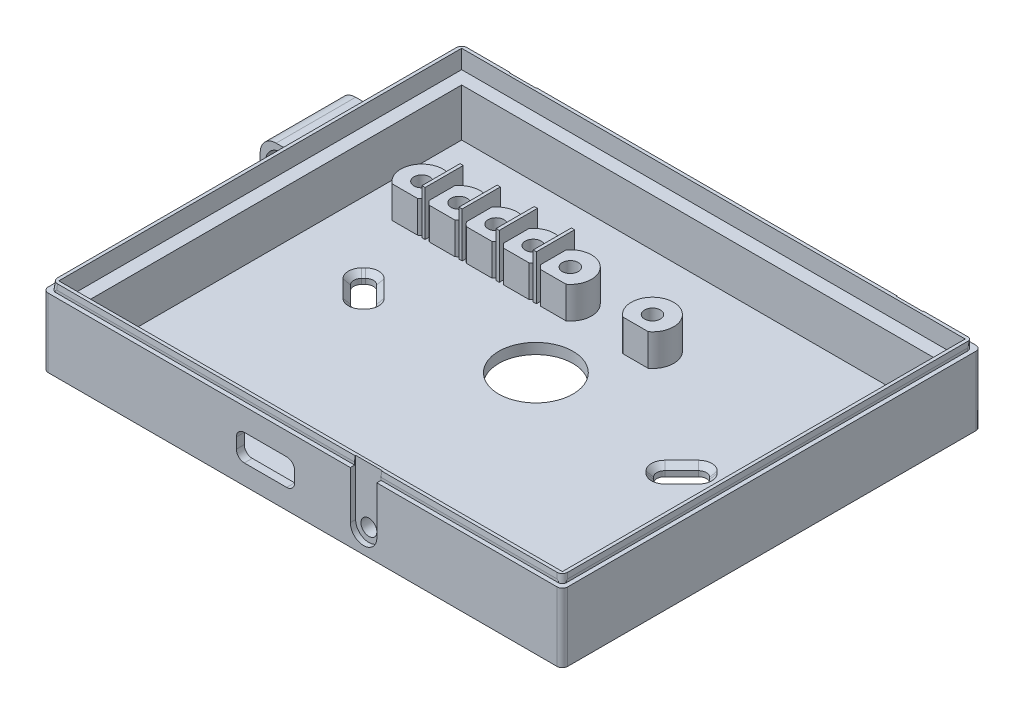
SolidWorks part; units mm, degrees
ref_plane "Alzado" through (0, 0, 0) normal (0, 0, 1) x (1, 0, 0)
ref_plane "Planta" through (0, 0, 0) normal (0, 1, 0) x (1, 0, 0)
ref_plane "Vista lateral" through (0, 0, 0) normal (1, 0, 0) x (0, 0, -1)
sketch "Croquis1" plane through (0, 0, 0) normal (0, 1, 0) x (1, 0, 0)
  line L1 (0, 0) -> (98, 0)
  line L2 (0, 0) -> (0, 79)
  line L3 (0, 79) -> (98, 79)
  line L4 (98, 0) -> (98, 79)
  line L5 (0, 0) -> (98, 79) construction
  line L6 (0, 79) -> (98, 0) construction
  point P4 (49, 39.5)
  dimension "D1" = 98
  dimension "D2" = 79
extrude "Saliente-Extruir1" add sketch "Croquis1" along normal blind 13
sketch "Croquis2" plane through (0, 13, 0) normal (0, 1, 0) x (1, 0, 0)
  line L0 (98, 0) -> (98, 79) construction
  line L1 (1.5, 77.5) -> (96.5, 77.5)
  line L2 (1.5, 77.5) -> (1.5, 1.5)
  line L3 (1.5, 1.5) -> (96.5, 1.5)
  line L4 (96.5, 77.5) -> (96.5, 1.5)
  line L5 (1.5, 77.5) -> (96.5, 1.5) construction
  line L6 (1.5, 1.5) -> (96.5, 77.5) construction
  line L7 (98, 79) -> (0, 79) construction
  point P4 (49, 39.5)
  dimension "D1" = 95
  dimension "D2" = 76
  dimension "D3" = 1.5
  dimension "D4" = 1.5
extrude "Cortar-Extruir1" cut sketch "Croquis2" against normal blind 11
sketch "Croquis3" plane through (0, 2, 0) normal (0, 1, 0) x (1, 0, 0)
  line L0 (24.5, 4) -> (24.5, 1.5)
  line L1 (1.5, 77.5) -> (96.5, 77.5)
  line L2 (1.5, 77.5) -> (1.5, 1.5)
  line L3 (1.5, 1.5) -> (24.5, 1.5)
  line L4 (96.5, 77.5) -> (96.5, 1.5)
  line L5 (1.5, 77.5) -> (96.5, 1.5) construction
  line L6 (1.5, 1.5) -> (96.5, 77.5) construction
  line L7 (4, 75) -> (94, 75)
  line L8 (4, 75) -> (4, 4)
  line L9 (4, 4) -> (24.5, 4)
  line L10 (94, 75) -> (94, 4)
  line L11 (4, 75) -> (94, 4) construction
  line L12 (4, 4) -> (94, 75) construction
  line L13 (58.5, 4) -> (58.5, 1.5)
  line L14 (58.5, 4) -> (94, 4)
  line L15 (58.5, 1.5) -> (96.5, 1.5)
  point P4 (49, 39.5)
  point P11 (49, 39.5)
  dimension "D1" = 2.5
  dimension "D2" = 2.5
  dimension "D3" = 2.5
  dimension "D4" = 2.5
  dimension "D5" = 38
  dimension "D6" = 23
extrude "Saliente-Extruir2" add sketch "Croquis3" along normal blind 9
sketch "Croquis4" plane through (0, 2, 0) normal (0, 1, 0) x (1, 0, 0)
  line L0 (13, 58.5) -> (56.5, 58.5) construction
  line L1 (96.5, 77.5) -> (1.5, 77.5) construction
  line L2 (1.5, 77.5) -> (1.5, 1.5) construction
  line L3 (10.6, 55.3) -> (15.4, 55.3)
  line L8 (54.1, 55.3) -> (58.9, 55.3)
  line L9 (17.6, 55.3) -> (22.4, 55.3)
  line L10 (24.6, 55.3) -> (29.4, 55.3)
  line L11 (31.6, 55.3) -> (36.4, 55.3)
  line L12 (38.6, 55.3) -> (43.4, 55.3)
  arc A0 (16.5, 60.4365) -> (10.6, 55.3) centre (13, 58.5) ccw
  arc A1 (16.5, 56.5635) -> (17.6, 55.3) centre (20, 58.5) ccw
  arc A2 (23.5, 56.5635) -> (24.6, 55.3) centre (27, 58.5) ccw
  arc A3 (30.5, 56.5635) -> (31.6, 55.3) centre (34, 58.5) ccw
  arc A4 (37.5, 56.5635) -> (38.6, 55.3) centre (41, 58.5) ccw
  arc A5 (58.9, 55.3) -> (54.1, 55.3) centre (56.5, 58.5) ccw
  arc A6 (23.5, 60.4365) -> (16.5, 60.4365) centre (20, 58.5) ccw
  arc A7 (30.5, 60.4365) -> (23.5, 60.4365) centre (27, 58.5) ccw
  arc A8 (37.5, 60.4365) -> (30.5, 60.4365) centre (34, 58.5) ccw
  circle A9 centre (13, 58.5) radius 1.5
  circle A10 centre (20, 58.5) radius 1.5
  circle A11 centre (27, 58.5) radius 1.5
  circle A12 centre (34, 58.5) radius 1.5
  circle A13 centre (41, 58.5) radius 1.5
  circle A14 centre (56.5, 58.5) radius 1.5
  arc A15 (15.4, 55.3) -> (16.5, 56.5635) centre (13, 58.5) ccw
  arc A16 (22.4, 55.3) -> (23.5, 56.5635) centre (20, 58.5) ccw
  arc A17 (29.4, 55.3) -> (30.5, 56.5635) centre (27, 58.5) ccw
  arc A18 (36.4, 55.3) -> (37.5, 56.5635) centre (34, 58.5) ccw
  arc A19 (43.4, 55.3) -> (37.5, 60.4365) centre (41, 58.5) ccw
  point P29 (27, 59.0244)
  dimension "D3" = 8
  dimension "D9" = 3
  dimension "D10" = 4
  dimension "D12" = 4
  dimension "D13" = 4
  dimension "D14" = 4
  dimension "D15" = 4
  dimension "D1" = 19
  dimension "D2" = 11.5
  dimension "D4" = 7
  dimension "D5" = 7
  dimension "D6" = 7
  dimension "D7" = 7
  dimension "D8" = 15.5
  dimension "D11" = 3.2
extrude "Saliente-Extruir3" add sketch "Croquis4" along normal blind 6
sketch "Croquis6" plane through (0, 2, 0) normal (0, 1, 0) x (1, 0, 0)
  line L0 (23.2, 62.5) -> (23.2, 55.3)
  line L1 (16.2, 62.5) -> (16.8, 62.5)
  line L2 (16.2, 62.5) -> (16.2, 55.3)
  line L3 (16.2, 55.3) -> (16.8, 55.3)
  line L4 (16.8, 62.5) -> (16.8, 55.3)
  line L5 (16.2, 62.5) -> (16.8, 55.3) construction
  line L6 (16.2, 55.3) -> (16.8, 62.5) construction
  line L7 (23.2, 62.5) -> (23.8, 62.5)
  line L8 (23.8, 62.5) -> (23.8, 55.3)
  line L9 (23.2, 55.3) -> (23.8, 55.3)
  line L10 (30.2, 62.5) -> (30.2, 55.3)
  line L11 (30.2, 62.5) -> (30.8, 62.5)
  line L12 (30.8, 62.5) -> (30.8, 55.3)
  line L13 (30.2, 55.3) -> (30.8, 55.3)
  line L14 (37.2, 62.5) -> (37.2, 55.3)
  line L15 (37.2, 62.5) -> (37.8, 62.5)
  line L16 (37.8, 62.5) -> (37.8, 55.3)
  line L17 (37.2, 55.3) -> (37.8, 55.3)
  circle A0 centre (13, 58.5) radius 1.5 construction
  circle A2 centre (13, 58.5) radius 1.5 construction
  point P4 (16.5, 58.9)
  dimension "D4" = 4
  dimension "D1" = 0.6
  dimension "D3" = 3.5
  dimension "D6" = 3.2
  dimension "D5" = 4
extrude "Saliente-Extruir4" add sketch "Croquis6" along normal blind 8.5
sketch "Croquis7" plane through (0, 2, 0) normal (0, 1, 0) x (1, 0, 0)
  line L0 (98, 0) -> (98, 79) construction
  line L1 (98, 79) -> (0, 79) construction
  line L6 (15.1109, 42.9142) -> (20.4142, 37.6109)
  line L7 (15.1109, 42.9142) -> (17.5858, 45.3891)
  line L8 (20.4142, 37.6109) -> (22.8891, 40.0858)
  line L9 (17.5858, 45.3891) -> (22.8891, 40.0858)
  line L10 (15.1109, 42.9142) -> (22.8891, 40.0858) construction
  line L11 (20.4142, 37.6109) -> (17.5858, 45.3891) construction
  line L12 (1.5, 1.5) -> (24.5, 1.5) construction
  line L13 (4, 4) -> (24.5, 4) construction
  line L14 (75.1109, 40.0858) -> (80.4142, 45.3891)
  line L15 (75.1109, 40.0858) -> (77.5858, 37.6109)
  line L16 (80.4142, 45.3891) -> (82.8891, 42.9142)
  line L17 (77.5858, 37.6109) -> (82.8891, 42.9142)
  line L18 (75.1109, 40.0858) -> (82.8891, 42.9142) construction
  line L19 (80.4142, 45.3891) -> (77.5858, 37.6109) construction
  line L20 (1.5, 1.5) -> (96.5, 1.5) construction
  circle A0 centre (49, 44) radius 7
  point P9 (19, 41.5)
  point P12 (79, 41.5)
  dimension "D1" = 14
  dimension "D2" = 49
  dimension "D3" = 35
  dimension "D4" = 3.5
  dimension "D5" = 7.5
  dimension "D6" = 30
  dimension "D7" = 40
  dimension "D8" = 45
  dimension "D9" = 30
  dimension "D10" = 45
  dimension "D11" = 40
  dimension "D12" = 3.5
  dimension "D13" = 7.5
extrude "Cortar-Extruir2" cut sketch "Croquis7" against normal blind 7.5
fillet "Redondeo1" radius 1.5 8 edges at (15.1109, 1, -42.9142) (17.5858, 1, -45.3891) (22.8891, 1, -40.0858) (20.4142, 1, -37.6109) (80.4142, 1, -45.3891) (82.8891, 1, -42.9142) (75.1109, 1, -40.0858) (77.5858, 1, -37.6109)
chamfer "Chaflán1" distance 1 angle 45 16 edges at (80.2374, 2, -40.2626) (82.2678, 2, -42.9142) (77.5858, 2, -38.2322) (81.6517, 2, -44.1517) (76.3483, 2, -38.8483) (80.4142, 2, -44.7678) (75.7322, 2, -40.0858) (77.7626, 2, -42.7374) (17.7626, 2, -40.2626) (20.4142, 2, -38.2322) (15.7322, 2, -42.9142) (21.6517, 2, -38.8483) (16.3483, 2, -44.1517) (22.2678, 2, -40.0858) (17.5858, 2, -44.7678) (20.2374, 2, -42.7374)
sketch "Croquis8" plane through (0, 13, 0) normal (0, 1, 0) x (1, 0, 0)
  line L1 (1.5, 77.5) -> (96.5, 77.5)
  line L2 (1.5, 77.5) -> (1.5, 1.5)
  line L3 (1.5, 1.5) -> (96.5, 1.5)
  line L4 (96.5, 77.5) -> (96.5, 1.5)
  line L5 (1.5, 77.5) -> (96.5, 1.5) construction
  line L6 (1.5, 1.5) -> (96.5, 77.5) construction
  line L7 (0.8, 78.2) -> (97.2, 78.2)
  line L8 (0.8, 78.2) -> (0.8, 0.8)
  line L9 (0.8, 0.8) -> (97.2, 0.8)
  line L10 (97.2, 78.2) -> (97.2, 0.8)
  line L11 (0.8, 78.2) -> (97.2, 0.8) construction
  line L12 (0.8, 0.8) -> (97.2, 78.2) construction
  point P4 (49, 39.5)
  point P11 (49, 39.5)
  dimension "D1" = 0.7
  dimension "D2" = 0.7
  dimension "D3" = 0.7
  dimension "D4" = 0.7
extrude "Saliente-Extruir6" add sketch "Croquis8" along normal blind 1.5
chamfer "Chaflán2" distance 1 angle 5 4 edges at (49, 14.5, -78.2) (0.8, 14.5, -39.5) (49, 14.5, -0.8) (97.2, 14.5, -39.5) first distance on face at (49, 13.75, -78.2) first distance on face at (0.8, 13.75, -39.5) first distance on face at (49, 13.75, -0.8) first distance on face at (97.2, 13.75, -39.5)
sketch "Croquis9" plane through (0, 0, 0) normal (0, 0, 1) x (1, 0, 0)
  line L1 (36.5, 8.75) -> (47.5, 8.75)
  line L2 (36.5, 8.75) -> (36.5, 3.75)
  line L3 (36.5, 3.75) -> (47.5, 3.75)
  line L4 (47.5, 8.75) -> (47.5, 3.75)
  line L5 (36.5, 8.75) -> (47.5, 3.75) construction
  line L6 (36.5, 3.75) -> (47.5, 8.75) construction
  line L7 (58.5, 11) -> (96.5, 11) construction
  line L8 (1.5, 11) -> (24.5, 11) construction
  line L9 (1.5, 11) -> (1.5, 14.5) construction
  line L10 (96.5, 11) -> (96.5, 14.5) construction
  line L11 (58.5, 11) -> (96.5, 11) construction
  line L12 (1.5, 11) -> (24.5, 11) construction
  line L13 (1.5, 11) -> (1.5, 14.5) construction
  line L14 (96.5, 11) -> (96.5, 14.5) construction
  point P4 (42, 6.25)
  dimension "D1" = 49
  dimension "D2" = 35
  dimension "D3" = 5
  dimension "D4" = 4.5
extrude "Cortar-Extruir3" cut sketch "Croquis9" against normal blind 10
fillet "Redondeo2" radius 1 8 edges at (0.8437, 14, -78.1563) (0.8437, 14, -0.8437) (97.1563, 14, -0.8437) (97.2, 13.25, -78.2) (98, 6.5, -79) (0, 6.5, -79) (0, 6.5, 0) (98, 6.5, 0)
fillet "Redondeo3" radius 1.5 4 edges at (36.5, 8.75, -0.75) (36.5, 3.75, -0.75) (47.5, 3.75, -0.75) (47.5, 8.75, -0.75)
ref_plane "Plano1" through (0, 0, -64) normal (0, 0, -1) x (-1, 0, 0)
sketch "Croquis10" plane through (0, 0, -64) normal (0, 0, -1) x (-1, 0, 0)
  line L0 (0, 13) -> (0, 0) construction
  line L1 (0, 2) -> (8, 2)
  line L2 (0, 2) -> (0, 10)
  line L3 (0, 10) -> (8, 10)
  line L4 (8, 2) -> (8, 10)
  line L5 (0, 2) -> (8, 10) construction
  line L6 (0, 10) -> (8, 2) construction
  line L7 (-97, 0) -> (-1, 0) construction
  circle A0 centre (4, 6) radius 3
  point P4 (4, 6)
  dimension "D3" = 6
  dimension "D1" = 2
  dimension "D2" = 8
  dimension "D4" = 8
extrude "Saliente-Extruir7" add sketch "Croquis10" against normal blind 15
fillet "Redondeo4" radius 3 2 edges at (-8, 2, -56.5) (-8, 10, -56.5)
sketch "Croquis11" plane through (0, 0, -79) normal (0, 0, -1) x (-1, 0, 0)
  line L1 (-97, 13) -> (-1, 13) construction
  line L2 (-96.2, 13) -> (-1.4597, 13) construction
  line L3 (-15, 13) -> (-15, 4)
  line L5 (-10, 4) -> (-10, 13)
  line L6 (0, 13) -> (0, 0) construction
  line L8 (-15, 13) -> (-15, 15)
  line L9 (-15, 15) -> (-10, 15)
  line L10 (-10, 13) -> (-10, 15)
  line L11 (-15, 13) -> (-10, 15) construction
  line L12 (-15, 15) -> (-10, 13) construction
  line L13 (-49, 38.4479) -> (-49, -19.2331) construction
  line L14 (-83, 13) -> (-83, 15)
  line L15 (-83, 15) -> (-88, 15)
  line L16 (-88, 13) -> (-88, 15)
  line L17 (-88, 4) -> (-88, 13)
  line L18 (-83, 13) -> (-83, 4)
  arc A0 (-10, 4) -> (-15, 4) centre (-12.5, 4) cw
  arc A1 (-88, 4) -> (-83, 4) centre (-85.5, 4) ccw
  point P14 (-12.5, 14)
  dimension "D1" = 9
  dimension "D2" = 5
  dimension "D3" = 2
  dimension "D4" = 10
  dimension "D5" = 49
extrude "Cortar-Extruir4" cut sketch "Croquis11" against normal blind 1
sketch "Croquis12" plane through (0, 0, -78) normal (0, 0, -1) x (-1, 0, 0)
  arc A0 (-15, 4) -> (-10, 4) centre (-12.5, 4) ccw construction
  arc A1 (-15, 4) -> (-10, 4) centre (-12.5, 4) ccw construction
  circle A2 centre (-12.5, 4) radius 1.5
  arc A3 (-88, 4) -> (-83, 4) centre (-85.5, 4) ccw construction
  arc A4 (-88, 4) -> (-83, 4) centre (-85.5, 4) ccw construction
  circle A5 centre (-85.5, 4) radius 1.5
  dimension "D1" = 3
  dimension "D2" = 3
extrude "Cortar-Extruir5" cut sketch "Croquis12" against normal blind 1
sketch "Croquis13" plane through (0, 0, 0) normal (0, 0, 1) x (1, 0, 0)
  line L0 (58, 13) -> (58, 4)
  line L1 (1.4597, 13) -> (96.5403, 13) construction
  line L2 (58, 4) -> (63, 4) construction
  line L3 (63, 4) -> (63, 13)
  line L4 (1, 13) -> (97, 13) construction
  line L5 (63, 13) -> (63, 15)
  line L6 (63, 15) -> (58, 15)
  line L7 (58, 15) -> (58, 13)
  line L8 (98, 13) -> (98, 0) construction
  arc A0 (58, 4) -> (63, 4) centre (60.5, 4) ccw
  dimension "D1" = 5
  dimension "D2" = 9
  dimension "D3" = 2
  dimension "D4" = 35
extrude "Cortar-Extruir6" cut sketch "Croquis13" against normal blind 1
sketch "Croquis14" plane through (0, 0, -1) normal (0, 0, 1) x (1, 0, 0)
  arc A0 (58, 4) -> (63, 4) centre (60.5, 4) ccw construction
  arc A1 (58, 4) -> (63, 4) centre (60.5, 4) ccw construction
  circle A2 centre (60.5, 4) radius 1.5
  dimension "D1" = 3
extrude "Cortar-Extruir7" cut sketch "Croquis14" against normal blind 6
